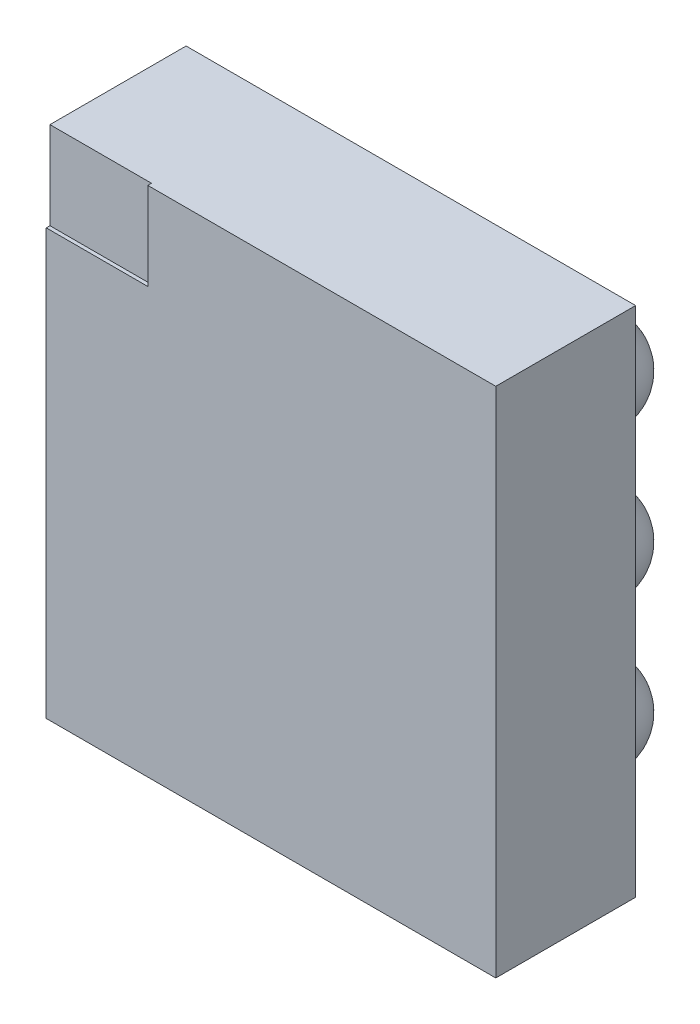
SolidWorks part; units mm, degrees
ref_plane "Front Plane" through (0, 0, 0) normal (0, 0, 1) x (1, 0, 0)
ref_plane "Top Plane" through (0, 0, 0) normal (0, 1, 0) x (1, 0, 0)
ref_plane "Right Plane" through (0, 0, 0) normal (1, 0, 0) x (0, 0, -1)
sketch "Sketch1" plane through (0, 0, 0) normal (0, 0, 1) x (1, 0, 0)
  line L1 (-0.6075, -0.6925) -> (0.6075, -0.6925)
  line L2 (-0.6075, -0.6925) -> (-0.6075, 0.6925)
  line L3 (-0.6075, 0.6925) -> (0.6075, 0.6925)
  line L4 (0.6075, -0.6925) -> (0.6075, 0.6925)
  line L5 (-0.6075, -0.6925) -> (0.6075, 0.6925) construction
  line L6 (-0.6075, 0.6925) -> (0.6075, -0.6925) construction
  point P0 (0, 0)
  dimension "D1" = 1.385
  dimension "D2" = 1.215
extrude "Boss-Extrude1" add sketch "Sketch1" along normal blind 0.378 from offset 0.203
sketch "Sketch2" plane through (0, 0, 0.581) normal (0, 0, 1) x (1, 0, 0)
  line L1 (-0.6075, 0.6925) -> (-0.3331, 0.6925)
  line L2 (-0.6075, 0.6925) -> (-0.6075, 0.4559)
  line L3 (-0.6075, 0.4559) -> (-0.3331, 0.4559)
  line L4 (-0.3331, 0.6925) -> (-0.3331, 0.4559)
extrude "Cut-Extrude1" cut sketch "Sketch2" against normal blind 0.01
sketch "Sketch3" plane through (0, 0, 0) normal (1, 0, 0) x (0, 0, -1)
  line L0 (-0.26, 0) -> (0, 0) construction
  line L1 (-0.203, 0) -> (0, 0)
  line L2 (-0.203, 0) -> (-0.203, -0.1076)
  line L4 (-0.203, -0.6925) -> (-0.203, 0.6925) construction
  arc A0 (-0.203, -0.1076) -> (0, 0) centre (-0.13, 0) ccw
  dimension "D1" = 0.26
revolve "Revolve1" add sketch "Sketch3" angle 360 about L0 region at (0, -0.0578, 0.1113)
pattern_linear "LPattern1" count 2 spacing 0.4 along (0, 1, 0) count 2 spacing 0.4 along (-1, 0, 0) of face at (-0.1076, 0, 0.203)
pattern_linear "LPattern2" count 3 spacing 0.4 along (1, 0, 0) count 3 spacing 0.4 along (0, -1, 0) skipping (0, 1), (1, 0), (1, 1) of face at (-0.5076, 0.4, 0.203)
